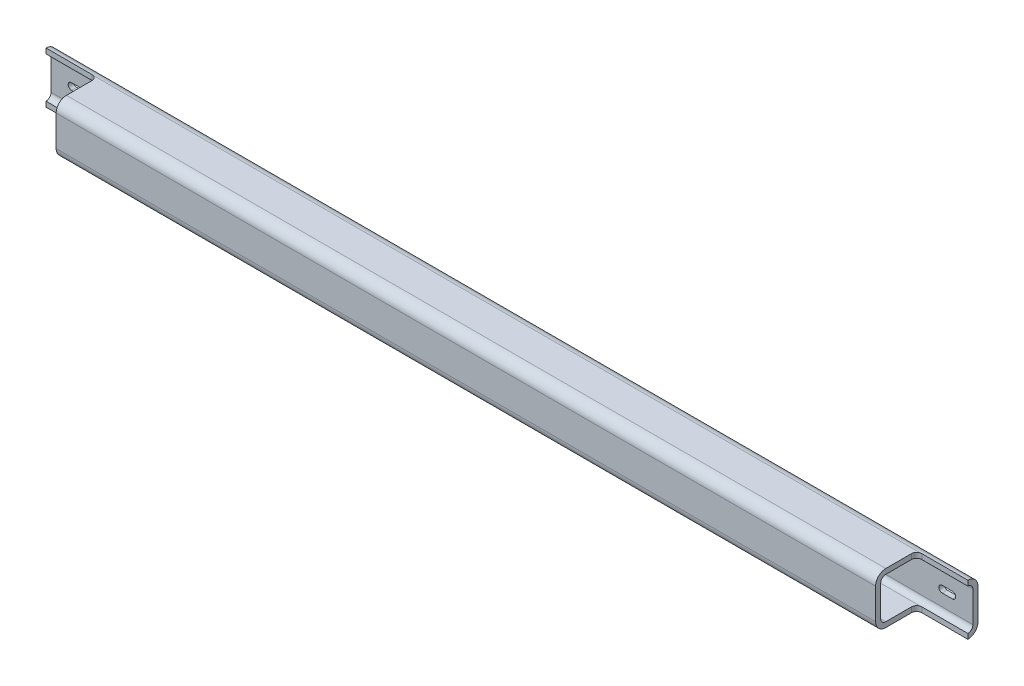
SolidWorks part; units mm, degrees
ref_plane "Front Plane" through (0, 0, 0) normal (0, 0, 1) x (1, 0, 0)
ref_plane "Top Plane" through (0, 0, 0) normal (0, 1, 0) x (1, 0, 0)
ref_plane "Right Plane" through (0, 0, 0) normal (1, 0, 0) x (0, 0, -1)
sketch "Sketch1" plane through (0, 0, 0) normal (0, 0, 1) x (1, 0, 0)
  line L0 (-450, 0) -> (450, 0)
  point P4 (0, 0)
  dimension "D1" = 900
other "Shs RHS50X50X5(1)" corner treatment miter
ref_plane "Plane1" through (-450, 0, 0) normal (1, 0, 0) x (0, 1, 0)
sketch "Sketch116" plane through (-450, 0, 0) normal (1, 0, 0) x (0, 1, 0)
  line L0 (-15, -20) -> (15, -20)
  line L1 (-20, -15) -> (-20, 15)
  line L2 (15, 20) -> (-15, 20)
  line L3 (20, 15) -> (20, -15)
  line L4 (-15, -25) -> (15, -25)
  line L5 (-25, -15) -> (-25, 15)
  line L6 (15, 25) -> (-15, 25)
  line L7 (25, 15) -> (25, -15)
  line L8 (-25, 0) -> (-20, 0) construction
  line L9 (-20, 0) -> (20, 0) construction
  line L10 (20, 0) -> (25, 0) construction
  line L11 (0, 25) -> (0, 20) construction
  line L12 (0, 20) -> (0, -20) construction
  line L13 (0, -20) -> (0, -25) construction
  arc A0 (25, 15) -> (15, 25) centre (15, 15) ccw
  arc A1 (15, -25) -> (25, -15) centre (15, -15) ccw
  arc A2 (-25, -15) -> (-15, -25) centre (-15, -15) ccw
  arc A3 (-15, 25) -> (-25, 15) centre (-15, 15) ccw
  arc A4 (-15, 20) -> (-20, 15) centre (-15, 15) ccw
  arc A5 (20, 15) -> (15, 20) centre (15, 15) ccw
  arc A6 (15, -20) -> (20, -15) centre (15, -15) ccw
  arc A7 (-20, -15) -> (-15, -20) centre (-15, -15) ccw
  point P6 (-25, 25)
  point P33 (0, 0)
  point P35 (25, 25)
  point P36 (-25, -25)
  point P37 (25, -25)
  point P38 (0, 0)
  dimension "D1" = 10
  dimension "Thickness" = 5
  dimension "V_leg" = 50
  dimension "H_leg" = 50
sketch "Sketch20" plane through (0, 0, 0) normal (0, 1, 0) x (1, 0, 0)
  line L0 (-400, -4.95) -> (400, -4.95) construction
  line L5 (0, -4.95) -> (0, 0) construction
  line L10 (450, -25) -> (400, -25)
  line L11 (450, -25) -> (450, 15.1)
  line L12 (450, 15.1) -> (400, 15.1)
  line L13 (400, -25) -> (400, 15.1)
  line L14 (-450, -25) -> (-400, -25)
  line L15 (-450, -25) -> (-450, 15.1)
  line L16 (-450, 15.1) -> (-400, 15.1)
  line L17 (-400, -25) -> (-400, 15.1)
  line L18 (450, -25) -> (-450, -25) construction
  line L19 (-450, 15) -> (-450, -15) construction
  line L20 (450, 15) -> (450, -15) construction
  dimension "D1" = 40.1
  dimension "D2" = 800
extrude "Cut-Extrude1" cut sketch "Sketch20" against normal through all both and the other way through all
fillet "Fillet1" radius 5 4 edges at (400, -22.4992, -15.1) (400, 22.4992, -15.1) (-400, -22.4992, -15.1) (-400, 22.4992, -15.1)
sketch "Sketch21" plane through (0, 0, -25) normal (0, 0, 1) x (-1, 0, 0)
  line L0 (-425, 0) -> (425, 0) construction
  line L1 (420, 0) -> (430, 0) construction
  line L2 (420, 3.25) -> (430, 3.25)
  line L3 (420, -3.25) -> (430, -3.25)
  line L4 (-430, 0) -> (-420, 0) construction
  line L5 (-430, 3.25) -> (-420, 3.25)
  line L6 (-430, -3.25) -> (-420, -3.25)
  circle A0 centre (-425, 0) radius 3.25 construction
  circle A1 centre (425, 0) radius 3.25 construction
  arc A2 (420, 3.25) -> (420, -3.25) centre (420, 0) ccw
  arc A3 (430, -3.25) -> (430, 3.25) centre (430, 0) ccw
  arc A4 (-430, 3.25) -> (-430, -3.25) centre (-430, 0) ccw
  arc A5 (-420, -3.25) -> (-420, 3.25) centre (-420, 0) ccw
  point P4 (0, 0)
  point P8 (425, 0)
  point P14 (-425, 0)
  dimension "D2" = 6.5
  dimension "D1" = 850
  dimension "D3" = 10
  dimension "D4" = 10
extrude "Cut-Extrude2" cut sketch "Sketch21" along normal blind 10
